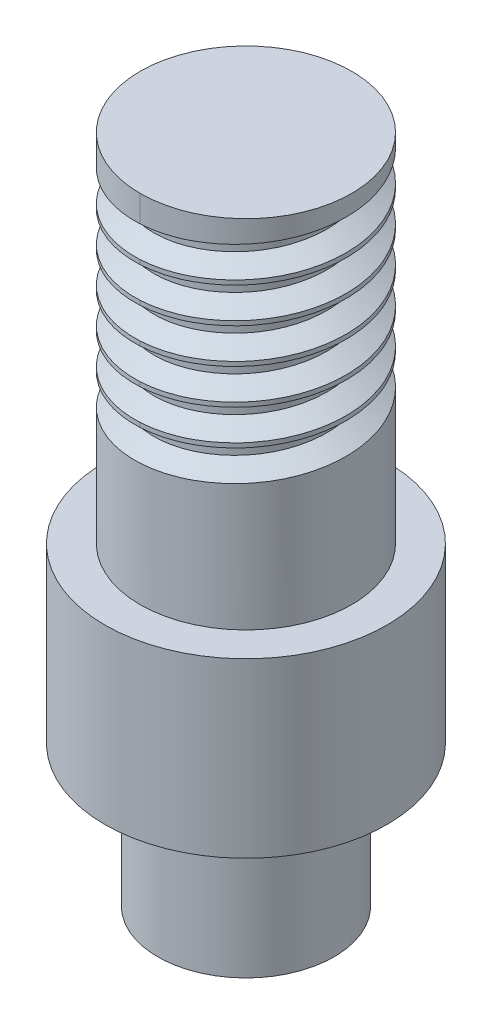
SolidWorks part; units mm, degrees
material "Plain Carbon Steel"
ref_plane "Front Plane" through (0, 0, 0) normal (0, 0, 1) x (1, 0, 0)
ref_plane "Top Plane" through (0, 0, 0) normal (0, 1, 0) x (1, 0, 0)
ref_plane "Right Plane" through (0, 0, 0) normal (1, 0, 0) x (0, 0, -1)
sketch "Sketch1" plane through (0, 0, 0) normal (0, 1, 0) x (1, 0, 0)
  circle A0 centre (0, 0) radius 4
  dimension "D1" = 8
extrude "Boss-Extrude1" add sketch "Sketch1" along normal blind 15
sketch "Sketch2" plane through (0, 15, 0) normal (0, 1, 0) x (1, 0, 0)
  circle A0 centre (0, 0) radius 4
  circle A1 centre (0, 0) radius 3
  dimension "D1" = 6
  dimension "D2" = 8
extrude "Cut-Extrude1" cut sketch "Sketch2" against normal blind 10.1
thread "Thread1" pitch 1 start angle 0, offset 0, length 0, pitch 1, diameter 6
ref_plane "Plane1" through (-3, 15, 0) normal (0, 0, 1) x (-1, 0, 0)
sketch "Thread Profile1" plane through (-3, 15, 0) normal (0, 0, 1) x (-1, 0, 0)
  line L0 (0, 0) -> (0, 1) construction
  line L11 (0, 0) -> (0, 0.875)
  line L12 (0, 0.875) -> (-0.5413, 0.5625)
  line L13 (-0.5413, 0.5625) -> (-0.5413, 0.3125)
  line L15 (-0.5413, 0.3125) -> (0, 0)
  line L17 (-0.5413, 0.4375) -> (0, 0.4375) construction
  point P2 (0, 0)
  dimension "Pitch" = 1
  dimension "Profile_Angle" = 60
  dimension "Profile_Land" = 0.25
  dimension "Profile_Height" = 0.5413
sketch "Sketch3" plane through (0, 0, 0) normal (0, -1, 0) x (1, 0, 0)
  circle A0 centre (0, 0) radius 2.5
  dimension "D1" = 5
extrude "Boss-Extrude2" add sketch "Sketch3" along normal blind 4
